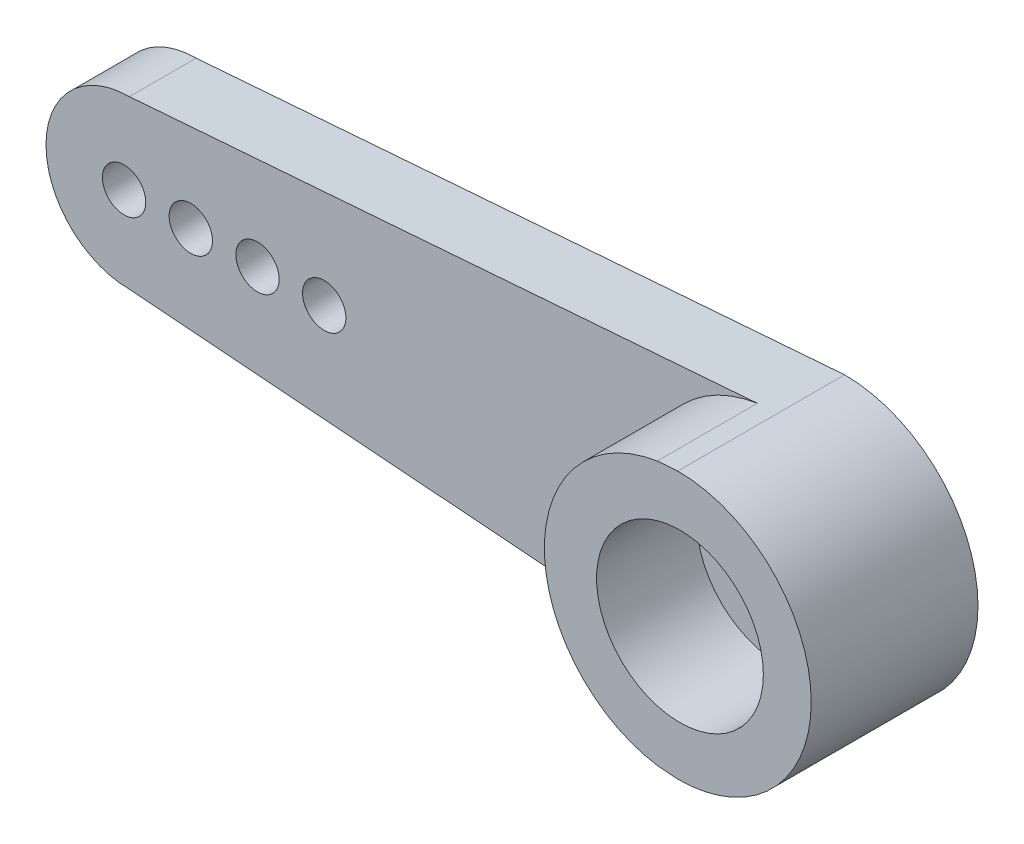
SolidWorks part; units mm, degrees
ref_plane "Plan de face" through (0, 0, 0) normal (0, 0, 1) x (1, 0, 0)
ref_plane "Plan de dessus" through (0, 0, 0) normal (0, 1, 0) x (1, 0, 0)
ref_plane "Plan de droite" through (0, 0, 0) normal (1, 0, 0) x (0, 0, -1)
sketch "Esquisse1" plane through (0, 0, 0) normal (0, 0, 1) x (1, 0, 0)
  line L0 (47.5059, 0) -> (-69.8402, 0) construction
  line L1 (-47.2901, 3) -> (-23.9621, 4.8)
  line L2 (-47.2901, -3) -> (-23.9621, -4.8)
  circle A0 centre (-23.9621, 0) radius 4.8
  arc A1 (-47.2901, 3) -> (-47.2901, -3) centre (-47.2901, 0) ccw
  dimension "D1" = 9.6
  dimension "D2" = 6
  dimension "D3" = 23.328
  dimension "D4" = 4.412
extrude "Boss.-Extru.1" add sketch "Esquisse1" along normal blind 2.4 contours L0 A0 L1 A1 | A0 L0 A1 L2 region at (-37.9266, -1.9101, 0) region at (-37.9266, 1.9101, 0)
extrude "Boss.-Extru.2" add sketch "Esquisse1<3>" along normal blind 6 contours L0 A0 L1 | A0 L0 L2 region at (-23.9621, -2.0367, 0) region at (-23.9621, 2.0367, 0)
sketch "Esquisse1<3>" plane through (0, 0, 0) normal (0, 0, 1) x (1, 0, 0) same geometry as "Esquisse1"
sketch "Esquisse2" plane through (0, 0, 2.4) normal (0, 0, 1) x (1, 0, 0)
  circle A0 centre (-47.4814, 0) radius 0.78
  circle A1 centre (-45.0814, 0) radius 0.78
  circle A2 centre (-42.6814, 0) radius 0.78
  circle A3 centre (-40.2814, 0) radius 0.78
  dimension "D1" = 1.56
  dimension "D2" = 1.56
  dimension "D3" = 1.56
  dimension "D4" = 1.56
  dimension "D5" = 2.4
  dimension "D6" = 2.4
  dimension "D7" = 2.4
extrude "Enlèv. mat.-Extru.1" cut sketch "Esquisse2" against normal through all
sketch "Esquisse3" plane through (0, 0, 0) normal (0, 0, -1) x (-1, 0, 0)
  circle A0 centre (23.9621, 0) radius 3.6
  dimension "D1" = 7.2
extrude "Enlèv. mat.-Extru.2" cut sketch "Esquisse3" against normal blind 0.6
sketch "Esquisse4" plane through (0, 0, 6) normal (0, 0, 1) x (1, 0, 0)
  circle A0 centre (-23.8841, 0) radius 3
  dimension "D1" = 6
extrude "Enlèv. mat.-Extru.3" cut sketch "Esquisse4" against normal blind 3.6
sketch "Esquisse5" plane through (0, 0, 2.4) normal (0, 0, 1) x (1, 0, 0)
  circle A0 centre (-23.8841, 0) radius 1.2
  dimension "D1" = 2.4
extrude "Enlèv. mat.-Extru.4" cut sketch "Esquisse5" against normal blind 3.6
